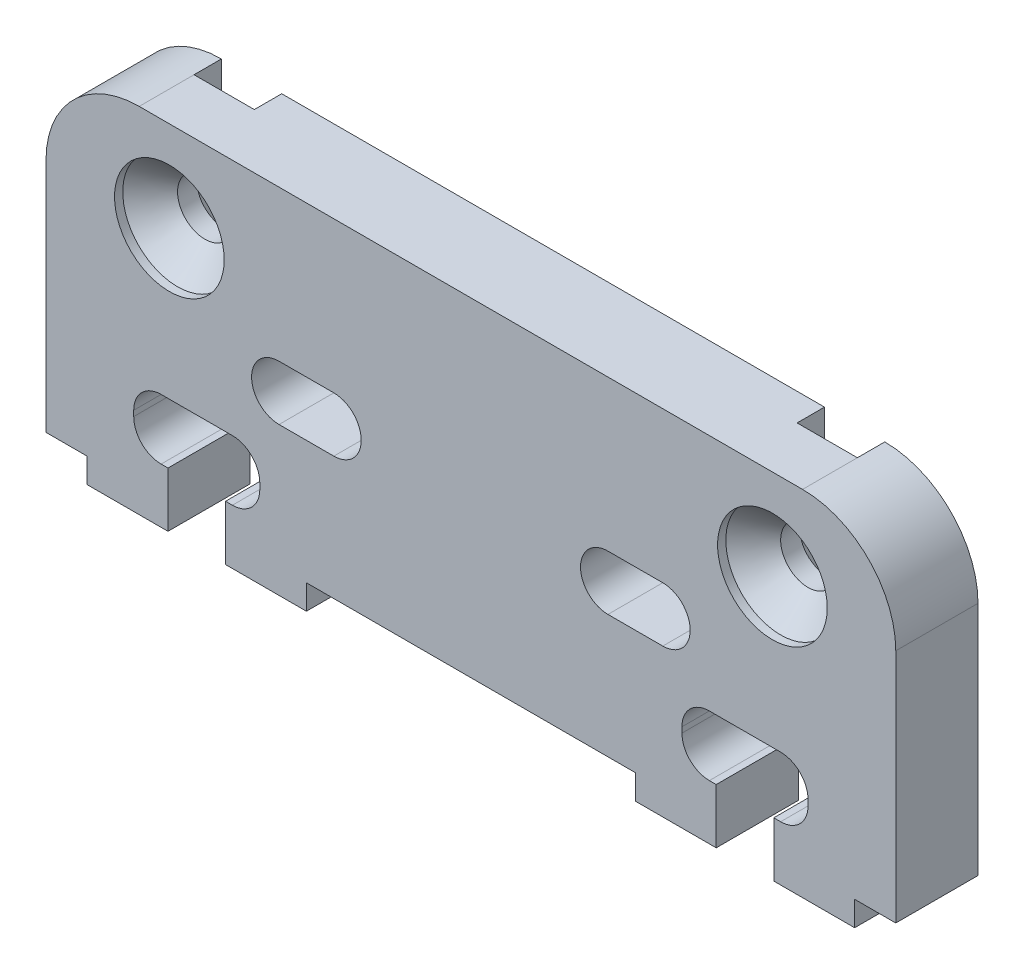
SolidWorks part; units mm, degrees
ref_plane "Front Plane" through (0, 0, 0) normal (0, 0, 1) x (1, 0, 0)
ref_plane "Top Plane" through (0, 0, 0) normal (0, 1, 0) x (1, 0, 0)
ref_plane "Right Plane" through (0, 0, 0) normal (1, 0, 0) x (0, 0, -1)
sketch "Sketch1" plane through (0, 0, 0) normal (0, 0, 1) x (1, 0, 0)
  line L0 (-10, -6.9) -> (-10, 6) construction
  line L1 (-15.5, 6) -> (15.5, 6)
  line L2 (-15.5, 6) -> (-15.5, -6)
  line L3 (-15.5, -6) -> (15.5, -6)
  line L4 (15.5, 6) -> (15.5, -6)
  line L5 (-15.5, 6) -> (15.5, -6) construction
  line L6 (-15.5, -6) -> (15.5, 6) construction
  line L7 (-15.5, -6) -> (-6, -6)
  line L9 (-14, -6.9) -> (-6, -6.9)
  line L10 (-6, -6) -> (-6, -6.9)
  line L11 (0, 6) -> (0, -6) construction
  line L12 (-11.05, -4.9) -> (-8.95, -4.9)
  line L13 (-11.05, -4.9) -> (-11.05, -6.9)
  line L14 (-11.05, -6.9) -> (-8.95, -6.9)
  line L15 (-8.95, -4.9) -> (-8.95, -6.9)
  line L16 (-11.05, -4.9) -> (-8.95, -6.9) construction
  line L17 (-11.05, -6.9) -> (-8.95, -4.9) construction
  line L18 (-12.3, -2.7) -> (-7.7, -2.7)
  line L19 (-12.3, -2.7) -> (-12.3, -4.9)
  line L20 (-12.3, -4.9) -> (-7.7, -4.9)
  line L21 (-7.7, -2.7) -> (-7.7, -4.9)
  line L22 (-12.3, -2.7) -> (-7.7, -4.9) construction
  line L23 (-12.3, -4.9) -> (-7.7, -2.7) construction
  line L24 (12.3, -2.7) -> (7.7, -2.7)
  line L25 (12.3, -2.7) -> (12.3, -4.9)
  line L26 (12.3, -4.9) -> (7.7, -4.9)
  line L27 (7.7, -2.7) -> (7.7, -4.9)
  line L28 (11.05, -4.9) -> (8.95, -4.9)
  line L29 (11.05, -4.9) -> (11.05, -6.9)
  line L30 (11.05, -6.9) -> (8.95, -6.9)
  line L31 (8.95, -4.9) -> (8.95, -6.9)
  line L32 (15.5, -6) -> (6, -6)
  line L33 (6, -6) -> (6, -6.9)
  line L34 (14, -6.9) -> (6, -6.9)
  line L36 (-14, -6.9) -> (-14, -6)
  line L37 (14, -6.9) -> (14, -6)
  line L38 (10, -2.7) -> (10, -6.9) construction
  line L39 (7, -0.5) -> (5, -0.5) construction
  line L40 (7, -1.5) -> (5, -1.5)
  line L41 (7, 0.5) -> (5, 0.5)
  line L42 (-7, -0.5) -> (-5, -0.5) construction
  line L43 (-7, -1.5) -> (-5, -1.5)
  line L44 (-7, 0.5) -> (-5, 0.5)
  arc A0 (7, -1.5) -> (7, 0.5) centre (7, -0.5) ccw
  arc A1 (5, 0.5) -> (5, -1.5) centre (5, -0.5) ccw
  arc A2 (-7, -1.5) -> (-7, 0.5) centre (-7, -0.5) cw
  arc A3 (-5, 0.5) -> (-5, -1.5) centre (-5, -0.5) cw
  point P0 (0, 0)
  point P11 (-10, -5.9)
  point P16 (-10, -3.8)
  point P40 (6, -0.5)
  point P47 (-6, -0.5)
  dimension "D1" = 31
  dimension "D2" = 12
  dimension "D3" = 0.9
  dimension "D4" = 8
  dimension "D5" = 2.1
  dimension "D6" = 2
  dimension "D7" = 2.2
  dimension "D8" = 4.6
  dimension "D9" = 20
  dimension "D10" = 2
  dimension "D11" = 2
  dimension "D12" = 12
  dimension "D13" = 5.5
extrude "Base shape" add sketch "Sketch1" along normal blind 3 contours L31 L26 L27 L24 L25 L29 L3 L4 L1 L2 L13 L20 L19 L18 L21 L15 | L3 L15 L9 L10 | L13 L3 L9 | L34 L31 L3 L33 | L3 L29 L34 region at (0, 0.3282, 0) region at (-12.525, -6.45, 0) region at (12.525, -6.45, 0) region at (-7.475, -6.45, 0) region at (7.475, -6.45, 0)
fillet "Edge radiuses" radius 3.4 2 edges at (15.5, 6, 1.5) (-15.5, 6, 1.5)
sketch "Sketch2" plane through (0, 0, 0) normal (0, 0, -1) x (-1, 0, 0)
  line L0 (0, 6) -> (0, -6) construction
  line L10 (12.1, 6) -> (-12.1, 6) construction
  line L11 (6, -6) -> (-6, -6) construction
  line L16 (-14, -6) -> (-15.5, -6) construction
  line L17 (-12.1, 6.1) -> (-9.9, 6.1)
  line L18 (-12.1, 6.1) -> (-12.1, 0.3)
  line L19 (-11.1, -0.7) -> (-10.9, -0.7)
  line L20 (-9.9, 6.1) -> (-9.9, 0.3)
  line L21 (-12.1, 6.1) -> (-9.9, -0.7) construction
  line L22 (-12.1, -0.7) -> (-9.9, 6.1) construction
  line L23 (12.1, 6.1) -> (9.9, 6.1)
  line L24 (12.1, 6.1) -> (12.1, 0.3)
  line L25 (11.1, -0.7) -> (10.9, -0.7)
  line L26 (9.9, 6.1) -> (9.9, 0.3)
  arc A8 (-10.9, -0.7) -> (-9.9, 0.3) centre (-10.9, 0.3) ccw
  arc A9 (-12.1, 0.3) -> (-11.1, -0.7) centre (-11.1, 0.3) ccw
  arc A10 (12.1, 0.3) -> (11.1, -0.7) centre (11.1, 0.3) cw
  arc A11 (10.9, -0.7) -> (9.9, 0.3) centre (10.9, 0.3) cw
  point P6 (-11, 2.7)
  dimension "D5" = 1
  dimension "D1" = 6.8
  dimension "D2" = 2.2
  dimension "D3" = 22
  dimension "D4" = 8.7
extrude "Camera mount pockets" cut sketch "Sketch2" against normal blind 1
sketch "Sketch3" plane through (0, 0, 1) normal (0, 0, -1) x (-1, 0, 0)
  line L3 (0, 6) -> (0, -6) construction
  line L5 (6, -6) -> (-6, -6) construction
  line L6 (-11.1, -0.7) -> (-10.9, -0.7) construction
  line L7 (-12.1, 6.1) -> (-9.9, 6.1)
  line L8 (-12.1, 6.1) -> (-12.1, -0.7)
  line L9 (-12.1, -0.7) -> (-9.9, -0.7)
  line L10 (-9.9, 6.1) -> (-9.9, -0.7)
  line L11 (-12.1, 6.1) -> (-9.9, -0.7) construction
  line L12 (-12.1, -0.7) -> (-9.9, 6.1) construction
  line L13 (-12.1, 6) -> (-12.1, 0.3) construction
  circle A0 centre (-11, 2.7) radius 1
  circle A1 centre (11, 2.7) radius 1
  point P2 (-11, 2.7)
  point P17 (-11, -0.7)
  point P18 (-11, -0.7)
  dimension "D1" = 2
  dimension "D2" = 6.8
extrude "Camera mount holes" cut sketch "Sketch3" against normal up to next contours A0 | A1 region at (11, 2.7, 1) region at (-11, 2.7, 1)
hole_wizard "CSK for M2 Flat Head Machine Screw1" positions "Sketch4" profile "Sketch5" countersink size "M2" standard "ANSI Metric" end condition through all
sketch "Sketch4" plane through (0, 0, 3) normal (0, 0, 1) x (1, 0, 0)
  point P0 (-11, 2.7)
  point P3 (11, 2.7)
sketch "Sketch5" plane through (-11, 2.7, 3) normal (1, 0, 0) x (0, -1, 0)
  line L0 (0, 0) -> (0, 3)
  line L1 (0, 3) -> (1, 3)
  line L2 (1, 3) -> (1, 1.3)
  line L3 (1, 1.3) -> (2, 0.3)
  line L4 (2, 0.3) -> (2, 0)
  line L6 (2, 0) -> (0, 0)
  line L7 (-1, 1.3) -> (-2, 0.3) construction
  line L11 (0, -6.35) -> (0, 107.95) construction
  dimension "Thru Hole Dia." = 2
  dimension "Thru Hole Depth" = 3
  dimension "C'Sink Dia." = 4
  dimension "C'Sink Angle" = 90
  dimension "Head Clearance" = 0.3
fillet "1mm milling radiuses" radius 1 8 edges at (-7.7, -2.7, 1.5) (-7.7, -4.9, 1.5) (12.3, -4.9, 1.5) (12.3, -2.7, 1.5) (7.7, -2.7, 1.5) (7.7, -4.9, 1.5) (-12.3, -4.9, 1.5) (-12.3, -2.7, 1.5)
sketch "Sketch7" plane through (0, -6.9, 0) normal (0, -1, 0) x (1, 0, 0)
  line L0 (-11.05, 3) -> (-8.95, 0) construction
  line L1 (7, 0) -> (13, 0)
  line L36 (0, 3) -> (0, 0) construction
  line L37 (-6, 3) -> (6, 3) construction
  line L38 (-6, 0) -> (6, 0) construction
  line L39 (-7, 3) -> (-13, 3)
  line L42 (-6, 2) -> (-6, 1)
  line L43 (-7, 0) -> (-13, 0)
  line L44 (-14, 2) -> (-14, 1)
  line L45 (-6, 3) -> (-14, 0) construction
  line L46 (-6, 0) -> (-14, 3) construction
  line L47 (6, 2) -> (6, 1)
  line L48 (7, 3) -> (13, 3)
  line L49 (14, 2) -> (14, 1)
  line L54 (-8.95, 0) -> (-6, 0)
  line L55 (-6, 0) -> (-6, 3)
  line L56 (-6, 3) -> (-8.95, 3)
  line L57 (-8.95, 3) -> (-8.95, 0)
  line L58 (-8.95, 0) -> (-6, 0)
  line L59 (-6, 0) -> (-6, 3)
  line L60 (-6, 3) -> (-8.95, 3)
  line L61 (-8.95, 3) -> (-8.95, 0)
  line L62 (-14, 0) -> (-11.05, 0)
  line L63 (-11.05, 0) -> (-11.05, 3)
  line L64 (-11.05, 3) -> (-14, 3)
  line L65 (-14, 3) -> (-14, 0)
  line L66 (-14, 0) -> (-11.05, 0)
  line L67 (-11.05, 0) -> (-11.05, 3)
  line L68 (-11.05, 3) -> (-14, 3)
  line L69 (-14, 3) -> (-14, 0)
  line L70 (6, 0) -> (8.95, 0)
  line L71 (8.95, 0) -> (8.95, 3)
  line L72 (8.95, 3) -> (6, 3)
  line L73 (6, 3) -> (6, 0)
  line L74 (6, 0) -> (8.95, 0)
  line L75 (8.95, 0) -> (8.95, 3)
  line L76 (8.95, 3) -> (6, 3)
  line L77 (6, 3) -> (6, 0)
  line L78 (11.05, 0) -> (14, 0)
  line L79 (14, 0) -> (14, 3)
  line L80 (14, 3) -> (11.05, 3)
  line L81 (11.05, 3) -> (11.05, 0)
  line L82 (11.05, 0) -> (14, 0)
  line L83 (14, 0) -> (14, 3)
  line L84 (14, 3) -> (11.05, 3)
  line L85 (11.05, 3) -> (11.05, 0)
  arc A4 (-6, 1) -> (-7, 0) centre (-7, 1) cw
  arc A5 (-7, 3) -> (-6, 2) centre (-7, 2) cw
  arc A6 (-13, 0) -> (-14, 1) centre (-13, 1) cw
  arc A7 (-13, 3) -> (-14, 2) centre (-13, 2) ccw
  arc A8 (6, 1) -> (7, 0) centre (7, 1) ccw
  arc A9 (7, 3) -> (6, 2) centre (7, 2) ccw
  arc A10 (13, 3) -> (14, 2) centre (13, 2) cw
  arc A11 (13, 0) -> (14, 1) centre (13, 1) ccw
  point P4 (-10, 1.5)
  dimension "D1" = 1
  dimension "D2" = 0
  dimension "D3" = 0
  dimension "D4" = 0
  dimension "D5" = 0
extrude "Top plate pocket radiuses" [suppressed] cut sketch "Sketch7" against normal up to surface (0.9 mm away) up to face at (14.75, -6, 1.5)
sketch "Slot sketch" plane through (0, 0, 1) normal (0, 0, -1) x (-1, 0, 0)
  line L0 (0, 6) -> (0, -6) construction
  line L3 (-12.1, 7.2) -> (-9.9, 7.2)
  line L4 (-12.1, 6) -> (-12.1, 0.3)
  line L5 (-11.1, -0.7) -> (-10.9, -0.7)
  line L6 (-9.9, 0.3) -> (-9.9, 6)
  line L7 (-9.9, 6) -> (-12.1, 6)
  line L9 (-11.1, -0.7) -> (-10.9, -0.7)
  line L12 (9.9, 6) -> (-9.9, 6) construction
  line L13 (6, -6) -> (-6, -6) construction
  line L25 (-12.1, 0.3) -> (-12.1, 7.2)
  line L26 (-9.9, 0.3) -> (-9.9, 7.2)
  line L27 (11.1, -0.7) -> (10.9, -0.7)
  line L28 (12.1, 0.3) -> (12.1, 7.2)
  line L29 (12.1, 7.2) -> (9.9, 7.2)
  line L30 (9.9, 0.3) -> (9.9, 7.2)
  arc A2 (-12.1, 0.3) -> (-11.1, -0.7) centre (-11.1, 0.3) ccw
  arc A3 (-10.9, -0.7) -> (-9.9, 0.3) centre (-10.9, 0.3) ccw
  arc A4 (-12.1, 0.3) -> (-11.1, -0.7) centre (-11.1, 0.3) ccw
  arc A5 (-10.9, -0.7) -> (-9.9, 0.3) centre (-10.9, 0.3) ccw
  arc A6 (10.9, -0.7) -> (9.9, 0.3) centre (10.9, 0.3) cw
  arc A7 (12.1, 0.3) -> (11.1, -0.7) centre (11.1, 0.3) cw
  dimension "D3" = 1.2
  dimension "D1" = 0
